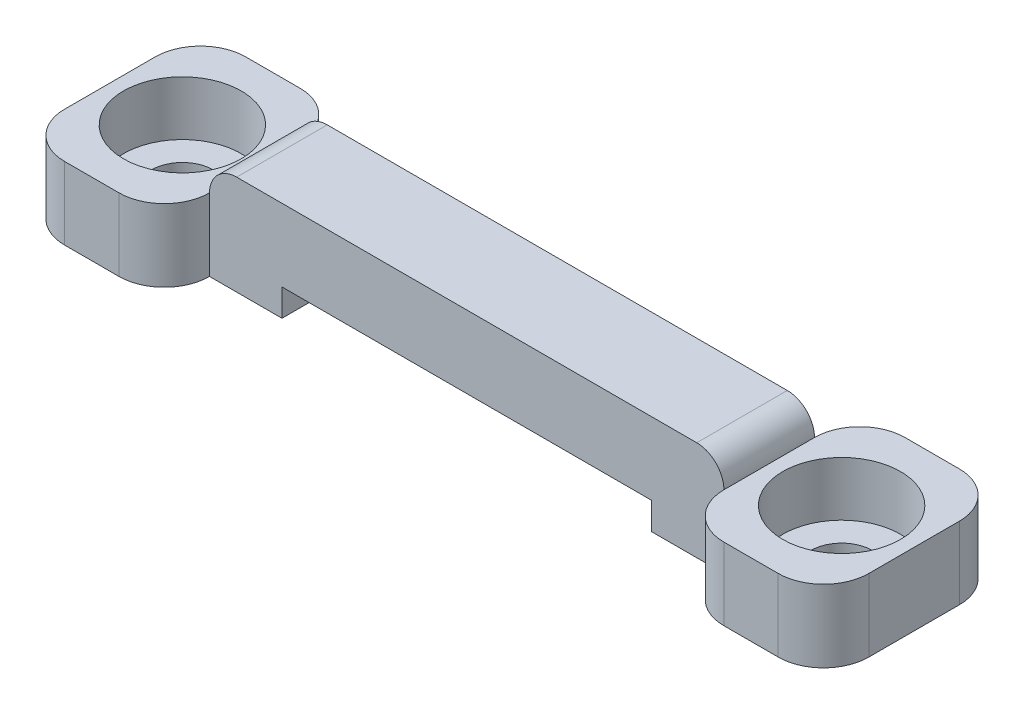
SolidWorks part; units mm, degrees
material "Filme de alta densidade PE"
ref_plane "Plano frontal" through (0, 0, 0) normal (0, 0, 1) x (1, 0, 0)
ref_plane "Plano superior" through (0, 0, 0) normal (0, 1, 0) x (1, 0, 0)
ref_plane "Plano direito" through (0, 0, 0) normal (1, 0, 0) x (0, 0, -1)
sketch "Esboço1" plane through (0, 0, 0) normal (0, 0, 1) x (1, 0, 0)
  line L0 (0, 0) -> (12, 0)
  line L1 (12, 0) -> (12, 1.5)
  line L2 (12, 1.5) -> (32.4, 1.5)
  line L3 (32.4, 1.5) -> (32.4, 0)
  line L4 (32.4, 0) -> (44.4, 0)
  line L5 (44.4, 0) -> (44.4, 4)
  line L6 (44.4, 4) -> (36.4, 4)
  line L7 (36.4, 4) -> (36.4, 5.5)
  line L8 (36.4, 5.5) -> (8, 5.5)
  line L9 (8, 5.5) -> (8, 4)
  line L10 (8, 4) -> (0, 4)
  line L11 (0, 4) -> (0, 0)
  point P3 (6, 8.1701)
  point P14 (22.2, 5.5)
  point P15 (22.2, 1.5)
  point P16 (8.9681, 0)
  point P17 (29.3143, 0)
  point P18 (33.0199, 4)
  dimension "D1" = 20.4
  dimension "D2" = 8
  dimension "D3" = 4
  dimension "D4" = 4
  dimension "D5" = 1.5
  dimension "D6" = 4
extrude "Ressalto-extrusão1" add sketch "Esboço1" along normal blind 10
hole_wizard "Rebaixo para SHCS M31" positions "Esboço2" profile "Esboço3" counterbore size "M3" standard "Ansi Metric" end condition through all
sketch "Esboço2" plane through (0, 4, 0) normal (0, 1, 0) x (1, 0, 0)
  line L0 (0, -5) -> (4, -5) construction
  line L1 (0, -10) -> (0, 0) construction
  line L3 (40.4, -5) -> (44.4, -5) construction
  line L4 (44.4, -10) -> (44.4, 0) construction
  point P0 (4, -5)
  point P2 (40.4, -5)
  dimension "D1" = 4
sketch "Esboço3" plane through (4, 4, 5) normal (1, 0, 0) x (0, 0, 1)
  line L0 (0, 0) -> (0, 4)
  line L1 (0, 4) -> (1.7, 4)
  line L3 (1.7, 4) -> (1.7, 3)
  line L4 (1.7, 3) -> (3.25, 3)
  line L5 (3.25, 3) -> (3.25, 0)
  line L7 (3.25, 0) -> (0, 0)
  line L11 (0, -6.35) -> (0, 107.95) construction
  dimension "Thru Hole Dia." = 3.4
  dimension "Thru Hole Depth" = 4
  dimension "C'Bore Dia." = 6.5
  dimension "C'Bore Depth" = 3
sketch "Esboço4" plane through (0, 0, 10) normal (0, 0, 1) x (1, 0, 0)
  line L0 (32.4, 0) -> (44.4, 0) construction
  line L1 (8, 5.5) -> (36.4, 5.5)
  line L2 (8, 5.5) -> (8, 0)
  line L3 (8, 0) -> (36.4, 0)
  line L4 (36.4, 5.5) -> (36.4, 0)
  line L5 (36.4, 4) -> (36.4, 5.5) construction
  point P7 (37.5819, 0)
extrude "Corte-extrusão1" cut sketch "Esboço4" against normal blind 2.5
sketch "Esboço5" plane through (0, 0, 0) normal (0, 0, -1) x (-1, 0, 0)
  line L0 (-32.4, 0) -> (-44.4, 0) construction
  line L1 (-36.4, 0) -> (-8, 0)
  line L2 (-36.4, 0) -> (-36.4, 5.5)
  line L3 (-36.4, 5.5) -> (-8, 5.5)
  line L4 (-8, 0) -> (-8, 5.5)
  line L5 (-36.4, 4) -> (-36.4, 5.5) construction
extrude "Corte-extrusão2" cut sketch "Esboço5" against normal blind 2.5
fillet "Filete1" radius 2.5 8 edges at (8, 2, 10) (0, 2, 10) (0, 2, 0) (8, 2, 0) (36.4, 2, 10) (44.4, 2, 10) (44.4, 2, 0) (36.4, 2, 0)
fillet "Filete2" radius 1.5 2 edges at (36.4, 5.5, 5) (8, 5.5, 5)
